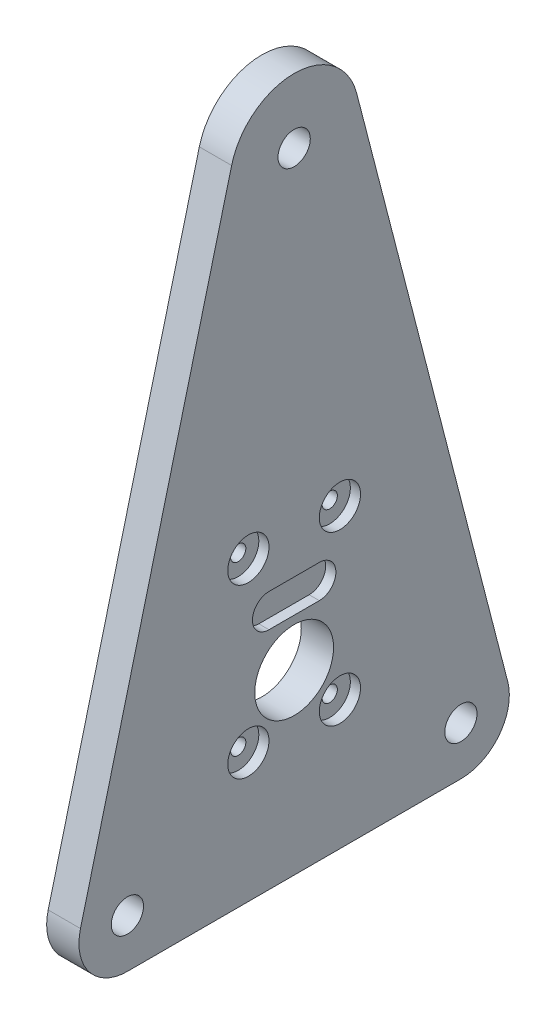
SolidWorks part; units mm, degrees
ref_plane "Front Plane" through (0, 0, 0) normal (0, 0, 1) x (1, 0, 0)
ref_plane "Top Plane" through (0, 0, 0) normal (0, 1, 0) x (1, 0, 0)
ref_plane "Right Plane" through (0, 0, 0) normal (1, 0, 0) x (0, 0, -1)
sketch "Sketch1" plane through (0, 0, 0) normal (1, 0, 0) x (0, 0, -1)
  line L0 (-12.4119, 117.475) -> (-33.9311, 34.1313)
  line L1 (12.1816, 117.475) -> (33.7008, 34.1313)
  line L2 (-0.1152, 25.4) -> (-0.1152, 114.3) construction
  line L4 (-33.9311, 34.1313) -> (-42.129, 2.3813)
  line L5 (33.7008, 34.1313) -> (41.8986, 2.3813)
  line L6 (-32.9064, -9.525) -> (32.6761, -9.525)
  arc A0 (-0.1152, -9.525) -> (33.7008, 34.1313) centre (-0.1152, 25.4) ccw construction
  arc A1 (12.1816, 117.475) -> (-12.4119, 117.475) centre (-0.1152, 114.3) ccw
  arc A2 (33.7008, 34.1313) -> (-33.9311, 34.1313) centre (-0.1152, 25.4) ccw construction
  arc A3 (-12.4119, 117.475) -> (12.1816, 117.475) centre (-0.1152, 114.3) ccw construction
  circle A4 centre (-0.1152, 114.3) radius 3.175
  circle A5 centre (-0.1152, 25.4) radius 7.75
  arc A6 (-33.9311, 34.1313) -> (-0.1152, -9.525) centre (-0.1152, 25.4) ccw construction
  arc A7 (41.8986, 2.3813) -> (32.6761, -9.525) centre (32.6761, 0) cw
  arc A8 (-32.9064, -9.525) -> (-42.129, 2.3813) centre (-32.9064, 0) cw
  circle A9 centre (-32.9064, 0) radius 3.175
  circle A10 centre (32.6761, 0) radius 3.175
  point P11 (27.4955, 4.0129)
  point P18 (-32.9064, 0)
  point P19 (32.6761, 0)
  dimension "D1" = 34.925
  dimension "D2" = 25.4
  dimension "D4" = 6.35
  dimension "D5" = 15.5
  dimension "D6" = 9.525
  dimension "D7" = 12.1816
  dimension "D8" = 6.35
  dimension "D3" = 88.9
extrude "Boss-Extrude1" add sketch "Sketch1" along normal blind 6.35
hole_wizard "CSK for M3 Flat Head Machine Screw1" positions "Sketch2" profile "Sketch3" hole size "Ø3.0" standard "ANSI Metric" end condition through all
sketch "Sketch2" plane through (0, 0, 0) normal (-1, 0, 0) x (0, 0, 1)
  point P0 (9.1152, 15.8606)
  point P3 (9.1152, 48.8606)
  point P6 (-8.8848, 48.8606)
  point P9 (-8.8848, 15.8606)
sketch "Sketch3" plane through (0, 15.8606, 9.1152) normal (0, 1, 0) x (0, 0, 1)
  line L0 (0, 0) -> (0, 6.35)
  line L1 (0, 6.35) -> (1.5, 6.35)
  line L2 (1.5, 6.35) -> (1.5, 0)
  line L5 (1.5, 0) -> (0, 0)
  line L11 (0, -6.35) -> (0, 107.95) construction
  dimension "Thru Hole Dia." = 3
  dimension "Thru Hole Depth" = 6.35
sketch "Sketch4" plane through (6.35, 0, 0) normal (1, 0, 0) x (0, 0, -1)
  line L0 (4.8348, 35) -> (-5.0652, 35) construction
  line L1 (-5.0652, 41) -> (4.8348, 41) construction
  line L2 (4.8348, 35) -> (-5.0652, 35) construction
  line L3 (-5.0652, 41) -> (4.8348, 41) construction
  line L4 (-5.0652, 41.254) -> (4.8348, 41.254)
  line L5 (4.8348, 34.746) -> (-5.0652, 34.746)
  circle A0 centre (8.8848, 15.8606) radius 3.8 construction
  circle A1 centre (-9.1152, 15.8606) radius 3.8 construction
  arc A2 (4.8348, 35) -> (4.8348, 41) centre (4.8348, 38) ccw construction
  arc A3 (-5.0652, 41) -> (-5.0652, 35) centre (-5.0652, 38) ccw construction
  circle A4 centre (8.8848, 48.8606) radius 3.8 construction
  circle A5 centre (-9.1152, 48.8606) radius 3.8 construction
  circle A6 centre (8.8848, 15.8606) radius 3.8 construction
  circle A7 centre (-9.1152, 15.8606) radius 3.8 construction
  arc A8 (4.8348, 35) -> (4.8348, 41) centre (4.8348, 38) ccw construction
  arc A9 (-5.0652, 41) -> (-5.0652, 35) centre (-5.0652, 38) ccw construction
  circle A10 centre (8.8848, 48.8606) radius 3.8 construction
  circle A11 centre (-9.1152, 48.8606) radius 3.8 construction
  circle A12 centre (-9.1152, 48.8606) radius 4.054
  circle A13 centre (8.8848, 48.8606) radius 4.054
  arc A14 (4.8348, 34.746) -> (4.8348, 41.254) centre (4.8348, 38) ccw
  arc A15 (-5.0652, 41.254) -> (-5.0652, 34.746) centre (-5.0652, 38) ccw
  circle A16 centre (-9.1152, 15.8606) radius 4.054
  circle A17 centre (8.8848, 15.8606) radius 4.054
  dimension "D1" = 0.254
extrude "Cut-Extrude1" cut sketch "Sketch4" against normal blind 2
